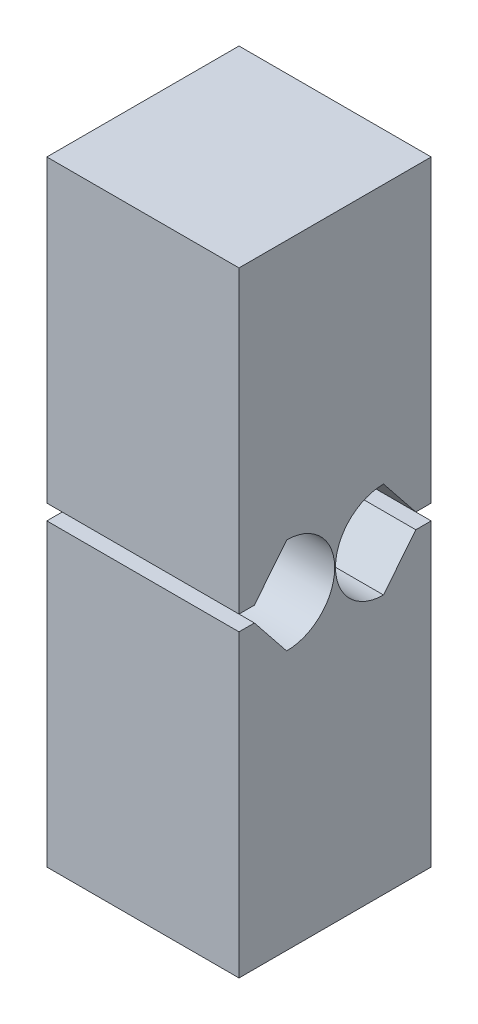
SolidWorks part; units mm, degrees
material "Beryllium Copper, UNS C17200"
ref_plane "Front Plane" through (0, 0, 0) normal (0, 0, 1) x (1, 0, 0)
ref_plane "Top Plane" through (0, 0, 0) normal (0, 1, 0) x (1, 0, 0)
ref_plane "Right Plane" through (0, 0, 0) normal (1, 0, 0) x (0, 0, -1)
sketch "Sketch1" plane through (0, 0, 0) normal (0, 1, 0) x (1, 0, 0)
  line L1 (-3.175, 3.175) -> (3.175, 3.175)
  line L2 (-3.175, 3.175) -> (-3.175, -3.175)
  line L3 (-3.175, -3.175) -> (3.175, -3.175)
  line L4 (3.175, 3.175) -> (3.175, -3.175)
  dimension "D1" = 3.175
  dimension "D2" = 3.175
  dimension "D3" = 3.175
  dimension "D4" = 3.175
extrude "Boss-Extrude1" add sketch "Sketch1" along normal mid plane 20.32
sketch "Sketch2" plane through (3.175, 0, 0) normal (1, 0, 0) x (0, 0, -1)
  line L0 (-3.175, 0.254) -> (-3.175, -0.254)
  line L1 (-3.175, 10.16) -> (-3.175, -10.16) construction
  line L2 (-3.175, -0.254) -> (-2.667, -0.254)
  line L3 (-2.667, -0.254) -> (-1.6002, -1.5875)
  line L4 (-3.175, 0.254) -> (-2.667, 0.254)
  line L5 (-2.667, 0.254) -> (-1.6002, 1.5875)
  arc A0 (-1.6002, 1.5875) -> (-1.6002, -1.5875) centre (-1.6002, 0) cw
  dimension "D1" = 0.254
  dimension "D2" = 0.254
  dimension "D3" = 0.508
  dimension "D4" = 0.508
extrude "Cut-Extrude1" cut sketch "Sketch2" against normal up to next
mirror "Mirror1" about plane through (0, 0, 0) normal (0, 0, 1) of "Cut-Extrude1"
sketch "Sketch3" plane through (-3.175, 0, 0) normal (-1, 0, 0) x (0, 0, 1)
  line L0 (-3.175, -10.16) -> (3.175, -10.16) construction
  point P0 (0, 0)
  dimension "D1" = 10.16
